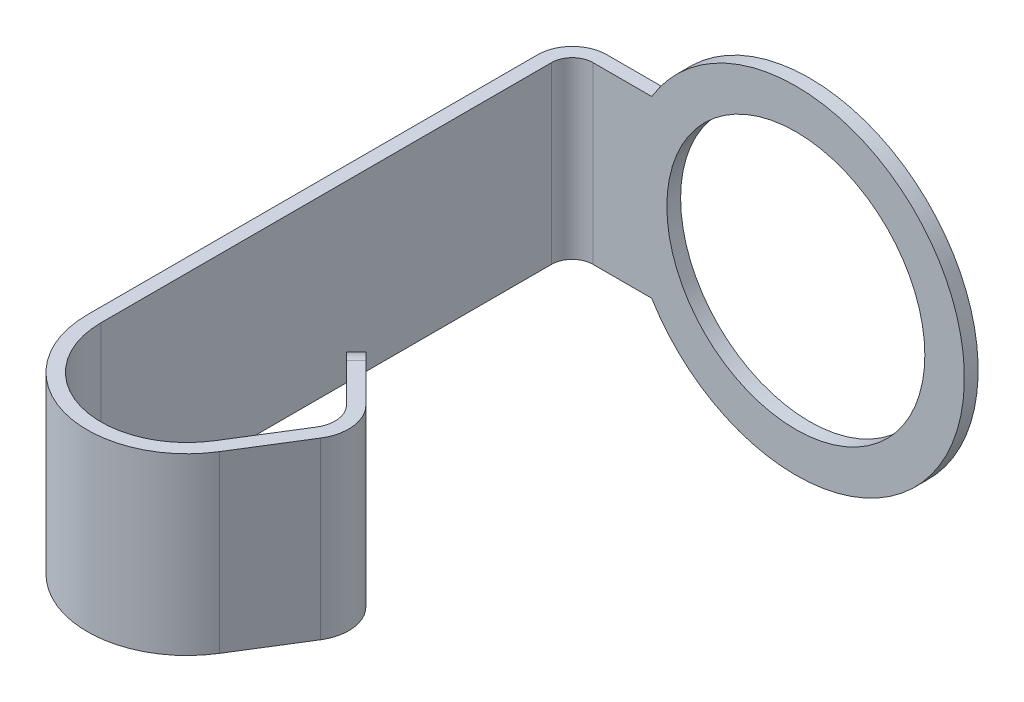
SolidWorks part; units mm, degrees
ref_plane "Front Plane" through (0, 0, 0) normal (0, 0, 1) x (1, 0, 0)
ref_plane "Top Plane" through (0, 0, 0) normal (0, 1, 0) x (1, 0, 0)
ref_plane "Right Plane" through (0, 0, 0) normal (1, 0, 0) x (0, 0, -1)
sketch "Sketch1" plane through (0, 0, 0) normal (0, 0, 1) x (1, 0, 0)
  circle A0 centre (0, 0) radius 6.223
  circle A1 centre (0, 0) radius 4.7625
extrude "Extrude1" add sketch "Sketch1" along normal blind 0.508
sketch "Sketch2" plane through (0, 0, 0) normal (0, 1, 0) x (1, 0, 0)
  line L0 (-6.223, 0) -> (-7.493, 0)
  line L2 (-6.223, 0) -> (-6.223, -0.508)
  line L4 (-6.223, -0.508) -> (-7.493, -0.508)
  line L5 (-8.763, -1.27) -> (-8.763, -17.907)
  line L8 (-8.255, -1.27) -> (-8.255, -17.907)
  line L10 (-0.5122, -17.5373) -> (-1.9446, -19.8393)
  line L12 (-0.9435, -17.2689) -> (-2.3765, -19.5719)
  line L15 (-0.7285, -15.6545) -> (-3.048, -13.335)
  line L16 (-1.0877, -16.0137) -> (-3.4072, -13.6942)
  line L17 (-3.048, -13.335) -> (-3.4072, -13.6942)
  arc A0 (-8.255, -1.27) -> (-7.493, -0.508) centre (-7.493, -1.27) cw
  arc A1 (-8.763, -1.27) -> (-7.493, 0) centre (-7.493, -1.27) cw
  arc A2 (-8.255, -17.907) -> (-2.3765, -19.5719) centre (-5.08, -17.907) ccw
  arc A3 (-8.763, -17.907) -> (-1.9446, -19.8393) centre (-5.08, -17.907) ccw
  arc A4 (-0.9435, -17.2689) -> (-1.0877, -16.0137) centre (-1.8061, -16.7321) ccw
  arc A5 (-0.5122, -17.5373) -> (-0.7285, -15.6545) centre (-1.8061, -16.7321) ccw
  dimension "D3" = 0.762
  dimension "D5" = 1.016
  dimension "D2" = 0.508
  dimension "D4" = 0.508
  dimension "D6" = 0.508
  dimension "D7" = 0.508
  dimension "D8" = 0.508
  dimension "D11" = 0.508
extrude "Extrude2" add sketch "Sketch2" along normal blind 3.2258 and the other way blind 3.2258
sketch "Sketch3" plane through (0, 0, 0) normal (0, 0, -1) x (-1, 0, 0)
  line L0 (6.223, 3.2258) -> (5.3216, 3.2258)
  line L1 (5.3216, 3.2258) -> (5.3216, -3.2258)
  line L2 (5.3216, -3.2258) -> (6.223, -3.2258)
  line L3 (6.223, -3.2258) -> (6.223, 3.2258)
  circle A0 centre (0, 0) radius 6.223 construction
extrude "Extrude3" add sketch "Sketch3" against normal blind 0.508
fillet "Fillet1" radius 1.27 2 edges at (-3.2276, 3.2258, 13.5146) (-3.2276, -3.2258, 13.5146)
